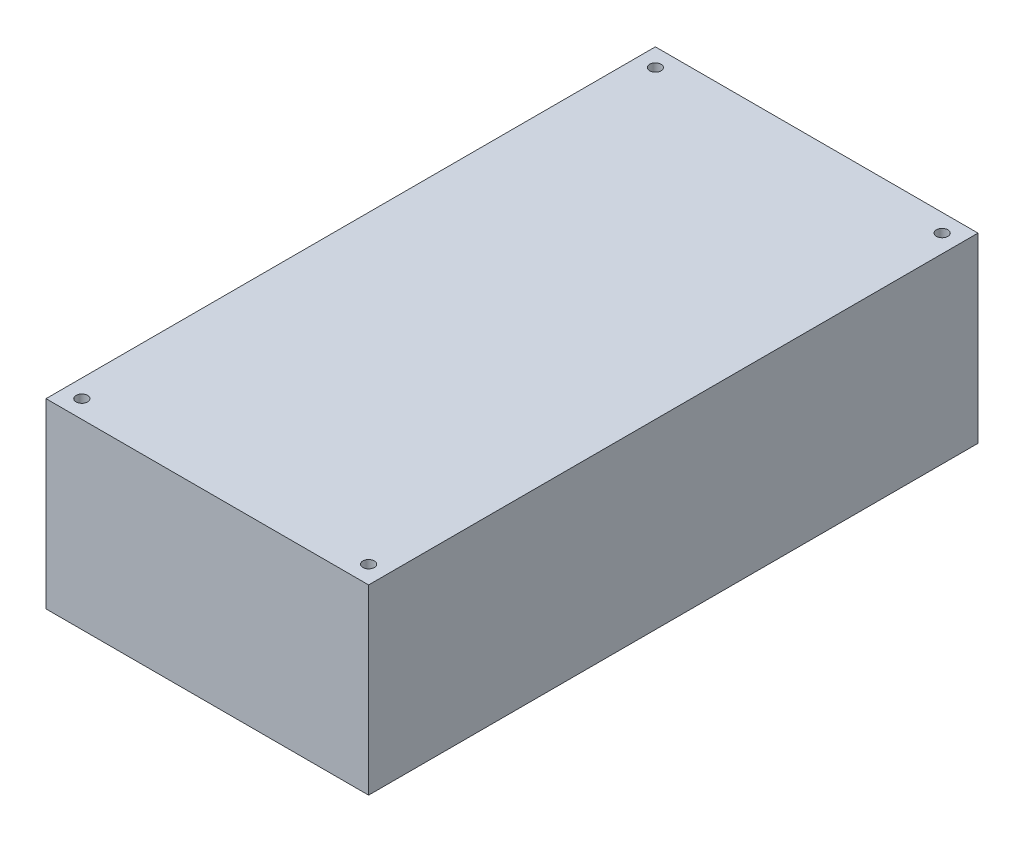
SolidWorks part; units mm, degrees
material "Silicon"
ref_plane "Front Plane" through (0, 0, 0) normal (0, 0, 1) x (1, 0, 0)
ref_plane "Top Plane" through (0, 0, 0) normal (0, 1, 0) x (1, 0, 0)
ref_plane "Right Plane" through (0, 0, 0) normal (1, 0, 0) x (0, 0, -1)
sketch "Sketch1" plane through (0, 0, 0) normal (0, 1, 0) x (1, 0, 0)
  line L1 (-35.5322, 109.623) -> (54.4678, 109.623)
  line L2 (-35.5322, 109.623) -> (-35.5322, -60.377)
  line L3 (-35.5322, -60.377) -> (54.4678, -60.377)
  line L4 (54.4678, 109.623) -> (54.4678, -60.377)
  dimension "D1" = 90
  dimension "D2" = 170
extrude "Boss-Extrude1" add sketch "Sketch1" along normal blind 50.8
sketch "Sketch2" plane through (0, 50.8, 0) normal (0, 1, 0) x (1, 0, 0)
  line L2 (9.4678, 109.623) -> (9.4678, -60.377) construction
  line L3 (-35.5322, 109.623) -> (54.4678, 109.623) construction
  line L4 (-35.5322, -60.377) -> (54.4678, -60.377) construction
  line L5 (-30.5322, 104.623) -> (49.4678, 104.623) construction
  line L6 (-35.5322, 109.623) -> (-35.5322, -60.377) construction
  line L7 (-35.5322, 24.623) -> (54.4678, 24.623) construction
  line L8 (54.4678, 109.623) -> (54.4678, -60.377) construction
  line L9 (49.4678, 104.623) -> (-30.5322, -55.377) construction
  circle A0 centre (-30.5322, 104.623) radius 1.6
  circle A1 centre (49.4678, 104.623) radius 1.6
  circle A2 centre (-30.5322, -55.377) radius 1.6
  circle A3 centre (49.4678, -55.377) radius 1.6
  point P14 (9.4678, 24.623)
  point P22 (9.4678, 24.623)
  dimension "D3" = 3.2
  dimension "D4" = 80
  dimension "D5" = 160
extrude "Cut-Extrude1" cut sketch "Sketch2" against normal blind 70.4
